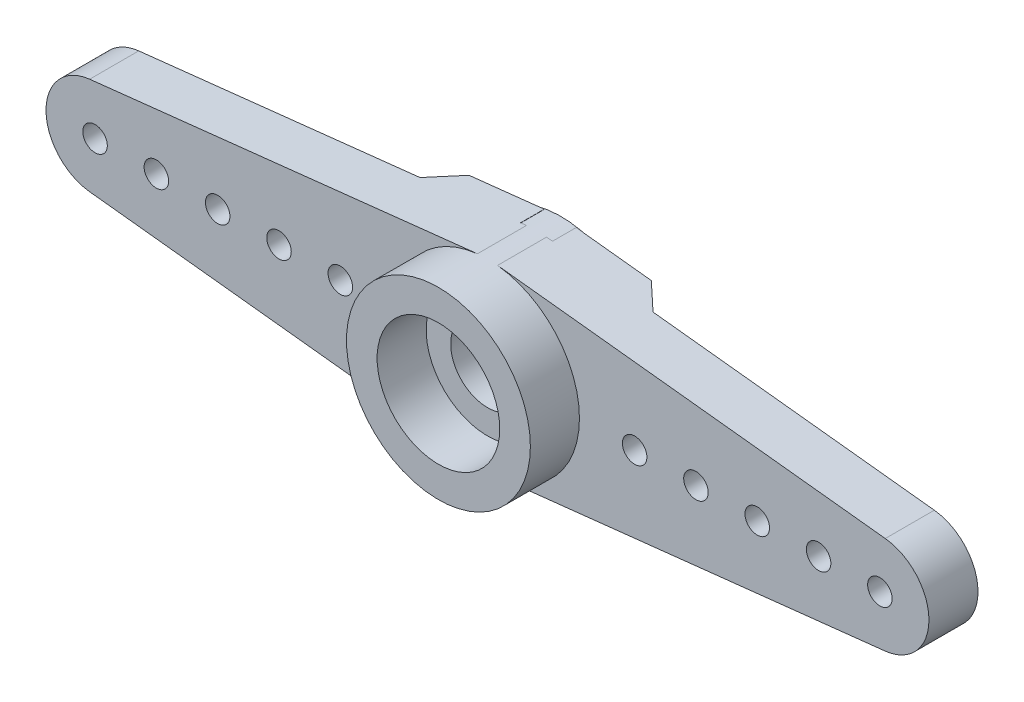
SolidWorks part; units mm, degrees
ref_plane "Front Plane" through (0, 0, 0) normal (0, 0, 1) x (1, 0, 0)
ref_plane "Top Plane" through (0, 0, 0) normal (0, 1, 0) x (1, 0, 0)
ref_plane "Right Plane" through (0, 0, 0) normal (1, 0, 0) x (0, 0, -1)
sketch "Croquis1" plane through (0, 0, 0) normal (0, 0, 1) x (1, 0, 0)
  line L0 (-18, 0) -> (18, 0) construction
  line L1 (-16, 0) -> (-18, 0) construction
  line L2 (-0.4102, 3.7275) -> (-16.2188, 1.988)
  line L3 (-16.2188, -1.988) -> (-0.4102, -3.7275)
  line L4 (0, 0) -> (0, 3.75) construction
  line L5 (16.2188, -1.988) -> (0.4102, -3.7275)
  line L6 (0.4102, 3.7275) -> (16.2188, 1.988)
  circle A0 centre (0, 0) radius 3.75
  circle A1 centre (0, 0) radius 2.5
  circle A2 centre (0, 0) radius 1.5
  circle A4 centre (-16, 0) radius 2
  circle A5 centre (16, 0) radius 2
  circle A6 centre (-16, 0) radius 0.5
  circle A7 centre (-13.5, 0) radius 0.5
  circle A8 centre (-11, 0) radius 0.5
  circle A9 centre (-8.5, 0) radius 0.5
  circle A10 centre (-6, 0) radius 0.5
  circle A11 centre (6, 0) radius 0.5
  circle A12 centre (8.5, 0) radius 0.5
  circle A13 centre (11, 0) radius 0.5
  circle A14 centre (13.5, 0) radius 0.5
  circle A15 centre (16, 0) radius 0.5
  point P8 (0, 0)
  dimension "D1" = 1
  dimension "D2" = 5
  dimension "D3" = 3
  dimension "D5" = 4
  dimension "D7" = 6
  dimension "D4" = 36
  dimension "D6" = 5
extrude "Saliente-Extruir1" add sketch "Croquis1" along normal mid plane 2 contours A4 A7 L3 A0 L2 A10 A9 A8 | A4 A6 | A0 A1 | A1 A2 | A5 A14 L6 A0 L5 A12 A11 A13 | A5 A15 region at (-3.9248, 0, 0) region at (0, 3.6439, 0) region at (-14.7031, 1.4474, 0) region at (8.2953, 2.684, 0) region at (17.4474, 1.2969, 0) region at (-2.4293, 0, 0)
extrude "Saliente-Extruir2" add sketch "Croquis1<3>" against normal blind 1 from surface contours A0 A1 region at (0, 3.6439, 0) starting at face at (14, 0, -1)
sketch "Croquis1<3>" plane through (0, 0, 0) normal (0, 0, 1) x (1, 0, 0) same geometry as "Croquis1"
extrude "Saliente-Extruir3" add sketch "Croquis1<4>" along normal blind 2 from surface contours A0 A1 region at (0, 3.6439, 0) starting at face at (14, 0, 1)
sketch "Croquis1<4>" plane through (0, 0, 0) normal (0, 0, 1) x (1, 0, 0) same geometry as "Croquis1"
sketch "Croquis3" plane through (0, 0, 0) normal (0, 1, 0) x (1, 0, 0)
  line L10 (-3.75, 1) -> (-4.75, 1) construction
  line L11 (-0.4102, 1) -> (-16.2188, 1) construction
  line L12 (-4.75, 1) -> (-3.6784, 2)
  line L13 (3.75, 2) -> (-3.75, 2) construction
  line L14 (-3.6784, 2) -> (-3.6784, 1)
  line L15 (-3.6784, 1) -> (-4.75, 1)
  line L16 (0, 0) -> (0, 2) construction
  line L17 (2.5, 2) -> (-2.5, 2) construction
  line L18 (3.6784, 1) -> (4.75, 1)
  line L19 (3.6784, 2) -> (3.6784, 1)
  line L20 (4.75, 1) -> (3.6784, 2)
  dimension "D1" = 1
extrude "Saliente-Extruir5" add sketch "Croquis3" along normal mid plane 1
sketch "Croquis4" plane through (0, 0, 0) normal (0, 1, 0) x (1, 0, 0)
  line L0 (-4.75, 1) -> (-0.6504, 1)
  line L1 (-0.4102, 1) -> (-16.2188, 1) construction
  line L2 (-4.75, 1) -> (-3.7165, 1.9644)
  line L3 (-3.7165, 1.9644) -> (-0.6504, 1.9644)
  line L4 (-0.6504, 1.9644) -> (-0.6504, 1)
  line L5 (0, 0) -> (0, 2) construction
  line L6 (3.75, 2) -> (-3.75, 2) construction
  line L7 (0.6504, 1.9644) -> (0.6504, 1)
  line L8 (4.75, 1) -> (0.6504, 1)
  line L9 (4.75, 1) -> (3.7165, 1.9644)
  line L10 (3.7165, 1.9644) -> (0.6504, 1.9644)
extrude "Saliente-Extruir6" add sketch "Croquis4" against normal blind 1 from offset 3.75
extrude "Saliente-Extruir7" add sketch "Croquis4<2>" along normal blind 1 from offset 3.75 offset against normal yes
sketch "Croquis4<2>" plane through (0, 0, 0) normal (0, 1, 0) x (1, 0, 0) same geometry as "Croquis4"
sketch "Croquis5" plane through (0, 0, -1) normal (0, 0, 1) x (1, 0, 0)
  line L0 (0.6504, -3.75) -> (4.75, -3.75)
  line L1 (4.75, -3.75) -> (4.75, -3.25)
  line L2 (4.75, -3.25) -> (0.6504, -3.7011)
  line L3 (0.6504, -3.7011) -> (0.6504, -3.75)
  line L4 (0, 0) -> (3.75, 0) construction
  line L5 (0, 0) -> (0, -3.75) construction
  line L6 (-0.6504, -3.7011) -> (-0.6504, -3.75)
  line L7 (-0.6504, -3.75) -> (-4.75, -3.75)
  line L8 (-4.75, -3.75) -> (-4.75, -3.25)
  line L9 (-4.75, -3.25) -> (-0.6504, -3.7011)
  line L11 (-4.75, 3.75) -> (-4.75, 3.25)
  line L12 (-0.6504, 3.75) -> (-4.75, 3.75)
  line L13 (-4.75, 3.25) -> (-0.6504, 3.7011)
  line L14 (-0.6504, 3.7011) -> (-0.6504, 3.75)
  line L15 (0.6504, 3.7011) -> (0.6504, 3.75)
  line L16 (0.6504, 3.75) -> (4.75, 3.75)
  line L17 (4.75, 3.25) -> (0.6504, 3.7011)
  line L18 (4.75, 3.75) -> (4.75, 3.25)
  arc A0 (0.4102, -3.7275) -> (0.4102, 3.7275) centre (0, 0) ccw construction
  circle A1 centre (0, 0) radius 3.75 construction
extrude "Cortar-Extruir1" cut sketch "Croquis5" against normal blind 3
